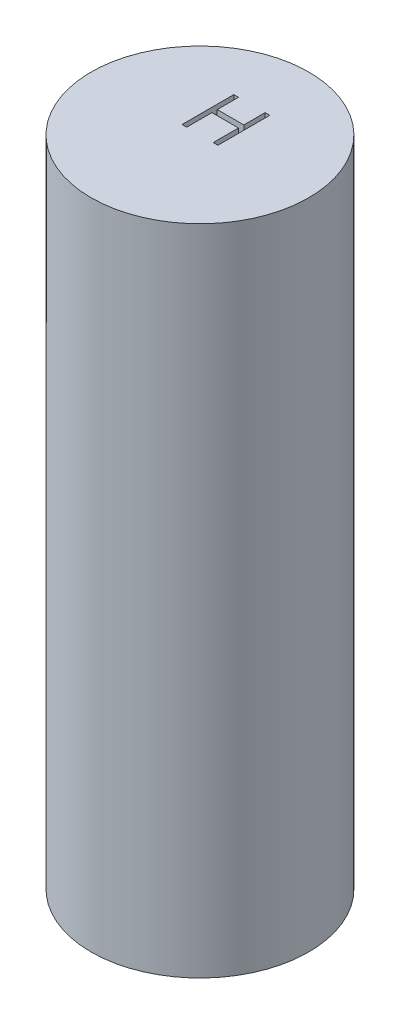
SolidWorks part; units mm, degrees
ref_plane "Front Plane" through (0, 0, 0) normal (0, 0, 1) x (1, 0, 0)
ref_plane "Top Plane" through (0, 0, 0) normal (0, 1, 0) x (1, 0, 0)
ref_plane "Right Plane" through (0, 0, 0) normal (1, 0, 0) x (0, 0, -1)
sketch "Sketch1" plane through (0, 0, 0) normal (0, 1, 0) x (1, 0, 0)
  circle A0 centre (0, 0) radius 10
  dimension "D1" = 20
extrude "Boss-Extrude1" add sketch "Sketch1" along normal blind 4
sketch "Sketch2" plane through (0, 4, 0) normal (0, 1, 0) x (1, 0, 0)
  circle A1 centre (0, 0) radius 1.5
  circle A2 centre (0, 0) radius 8
  circle A3 centre (0, 0) radius 8
  circle A4 centre (0, 0) radius 10 construction
  circle A5 centre (0, 0) radius 10
  circle M2 centre (0, 0) radius 10
  dimension "D2" = 3
  dimension "D1" = 2
extrude "Boss-Extrude2" add sketch "Sketch2" along normal blind 52 contours A1 | A3 M2 region at (0, 4, 0) region at (-9.7172, 4, 0)
sketch "Sketch3" plane through (0, 56, 0) normal (0, 1, 0) x (1, 0, 0)
  circle A0 centre (0, 0) radius 10 construction
  circle A1 centre (0, 0) radius 10
extrude "Boss-Extrude3" add sketch "Sketch3" along normal blind 4
sketch "Sketch4" plane through (0, 60, 0) normal (0, 1, 0) x (1, 0, 0)
  line L0 (-10, 0) -> (10, 0) construction
  circle A0 centre (0, 0) radius 10 construction
  text T0 "H" font "Century Gothic" height in points 18
extrude "Cut-Extrude1" cut sketch "Sketch4" against normal blind 2
